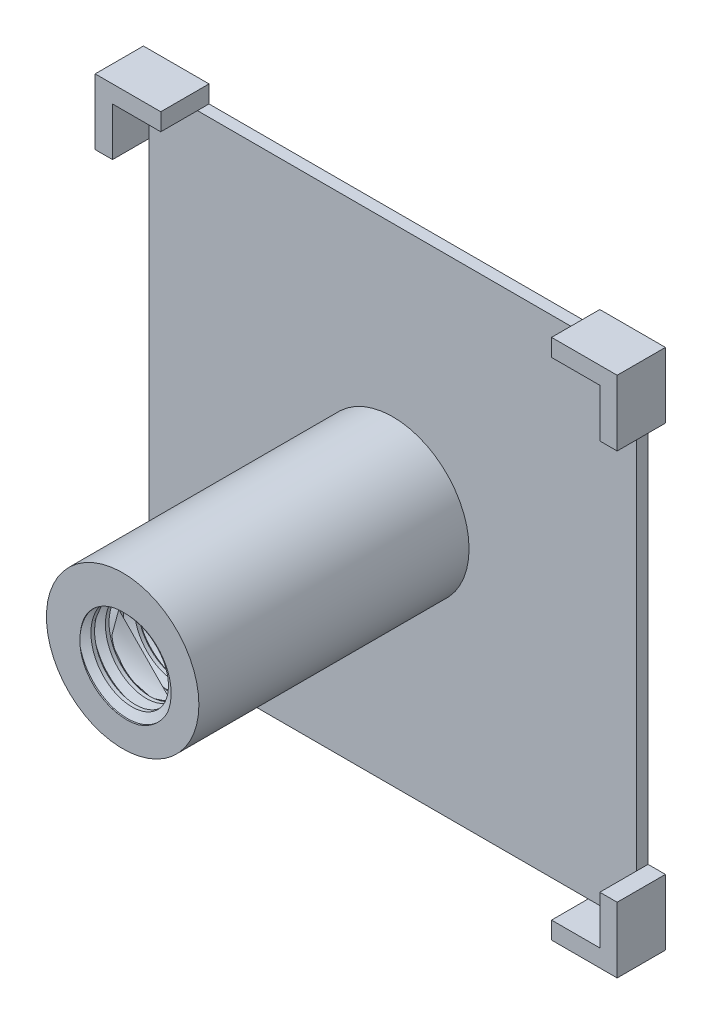
SolidWorks part; units mm, degrees
note: The reader was unsure of these and kept them because the rebuilt part matched: shared geometry of "Croquis4<2>".
ref_plane "Alzado" through (0, 0, 0) normal (0, 0, 1) x (1, 0, 0)
ref_plane "Planta" through (0, 0, 0) normal (0, 1, 0) x (1, 0, 0)
ref_plane "Vista lateral" through (0, 0, 0) normal (1, 0, 0) x (0, 0, -1)
sketch "Croquis1" plane through (0, 0, 0) normal (0, 0, 1) x (1, 0, 0)
  line L1 (-25.25, 25.25) -> (25.25, 25.25)
  line L2 (-25.25, 25.25) -> (-25.25, -25.25)
  line L3 (-25.25, -25.25) -> (25.25, -25.25)
  line L4 (25.25, 25.25) -> (25.25, -25.25)
  circle A0 centre (0, 0) radius 5.2
  point P4 (0, 25.25)
  point P6 (-25.25, 0)
  dimension "D3" = 10.4
  dimension "D1" = 50.5
  dimension "D2" = 50.5
extrude "Saliente-Extruir1" add sketch "Croquis1" along normal blind 1.2
sketch "Croquis2" plane through (0, 0, 1.2) normal (0, 0, 1) x (1, 0, 0)
  circle A0 centre (0, 0) radius 5.2
  circle A1 centre (0, 0) radius 7.9
  circle A2 centre (0, 0) radius 5.2 construction
  dimension "D1" = 2.7
extrude "Saliente-Extruir2" add sketch "Croquis2" along normal blind 28
thread "Rosca1" pitch 1.5 start angle 0, offset 2, length 0, pitch 1.5, diameter 10.4
ref_plane "Plano1" through (5.2, 0, -2) normal (0, -1, 0) x (1, 0, 0)
sketch "Perfil de rosca1" plane through (5.2, 0, -2) normal (0, -1, 0) x (1, 0, 0)
  line L0 (0, 0) -> (0, 1.5) construction
  line L11 (0, 0) -> (0, 1.3125)
  line L12 (0, 1.3125) -> (-0.8119, 0.8437)
  line L13 (-0.8119, 0.8437) -> (-0.8119, 0.4687)
  line L15 (-0.8119, 0.4687) -> (0, 0)
  line L17 (-0.8119, 0.6562) -> (0, 0.6562) construction
  point P2 (0, 0)
  dimension "Pitch" = 1.5
  dimension "Profile_Angle" = 60
  dimension "Profile_Land" = 0.375
  dimension "Profile_Height" = 0.8119
sketch "Croquis3" plane through (0, 0, 0) normal (0, 0, -1) x (-1, 0, 0)
  line L0 (25.25, -25.25) -> (25.25, -20.25)
  line L1 (25.25, 25.25) -> (25.25, -25.25) construction
  line L2 (25.25, -20.25) -> (27.05, -20.25)
  line L3 (27.05, -20.25) -> (27.05, -27.05)
  line L4 (27.05, -27.05) -> (20.25, -27.05)
  line L5 (20.25, -27.05) -> (20.25, -25.25)
  line L6 (25.25, -25.25) -> (-25.25, -25.25) construction
  line L7 (20.25, -25.25) -> (25.25, -25.25)
  line L8 (-25.25, -25.25) -> (-20.25, -25.25)
  line L9 (-20.25, -25.25) -> (-20.25, -27.05)
  line L10 (-20.25, -27.05) -> (-27.05, -27.05)
  line L11 (-27.05, -27.05) -> (-27.05, -20.25)
  line L12 (-27.05, -20.25) -> (-25.25, -20.25)
  line L13 (-25.25, -20.25) -> (-25.25, -25.25)
  line L14 (-25.25, 25.25) -> (-25.25, 20.25)
  line L15 (-25.25, 20.25) -> (-27.05, 20.25)
  line L16 (-27.05, 20.25) -> (-27.05, 27.05)
  line L17 (-27.05, 27.05) -> (-20.25, 27.05)
  line L18 (-20.25, 27.05) -> (-20.25, 25.25)
  line L19 (-20.25, 25.25) -> (-25.25, 25.25)
  line L20 (25.25, 25.25) -> (20.25, 25.25)
  line L21 (20.25, 25.25) -> (20.25, 27.05)
  line L22 (20.25, 27.05) -> (27.05, 27.05)
  line L23 (27.05, 27.05) -> (27.05, 20.25)
  line L24 (27.05, 20.25) -> (25.25, 20.25)
  line L25 (25.25, 20.25) -> (25.25, 25.25)
  line L26 (-25.25, 25.25) -> (25.25, 25.25) construction
  line L27 (25.25, 25.25) -> (25.25, -25.25) construction
  dimension "D1" = 5
  dimension "D2" = 5
  dimension "D3" = 1.8
  dimension "D4" = 1.8
  dimension "D5" = 4
extrude "Saliente-Extruir3" add sketch "Croquis3" against normal blind 5
sketch "Croquis4" plane through (0, 0, 29.2) normal (0, 0, 1) x (1, 0, 0)
  circle A0 centre (0, 0) radius 7.7
extrude "Cortar-Extruir1" cut sketch "Croquis4" along normal blind 10
extrude "Cortar-Extruir2" cut sketch "Croquis4<2>" against normal blind 10 from surface at -29.2 starting at face at (0, 0, 0)
sketch "Croquis4<2>" plane through (0, 0, 29.2) normal (0, 0, 1) x (1, 0, 0) same geometry as "Croquis4"
